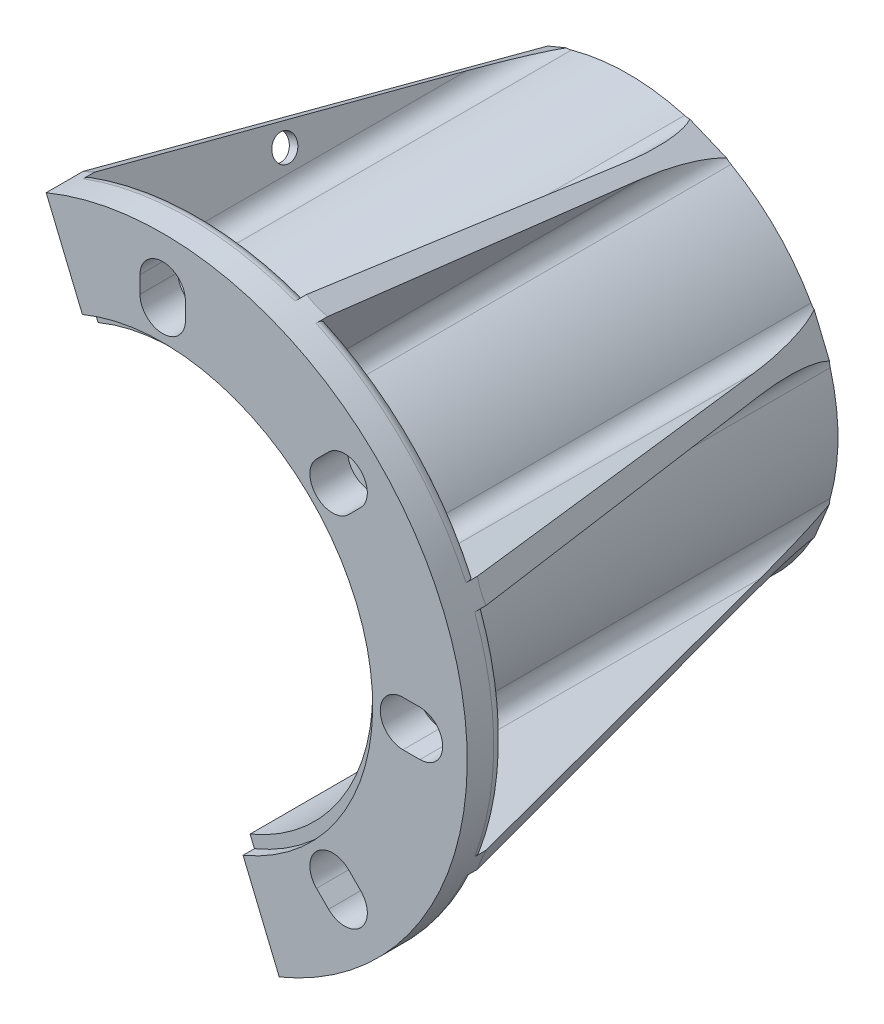
SolidWorks part; units mm, degrees
ref_plane "Front Plane" through (0, 0, 0) normal (0, 0, 1) x (1, 0, 0)
ref_plane "Top Plane" through (0, 0, 0) normal (0, 1, 0) x (1, 0, 0)
ref_plane "Right Plane" through (0, 0, 0) normal (1, 0, 0) x (0, 0, -1)
sketch "Sketch1" plane through (0, 0, 0) normal (0, 0, 1) x (1, 0, 0)
  line L0 (0, 0) -> (0, 80.5) construction
  line L1 (-6, 68) -> (-6, 63.5)
  line L2 (6, 68) -> (6, 63.5)
  line L3 (43.8406, 52.3259) -> (40.6586, 49.1439)
  line L4 (52.3259, 43.8406) -> (49.1439, 40.6586)
  line L5 (68, 6) -> (63.5, 6)
  line L6 (68, -6) -> (63.5, -6)
  line L7 (52.3259, -43.8406) -> (49.1439, -40.6586)
  line L8 (43.8406, -52.3259) -> (40.6586, -49.1439)
  line L9 (6, -68) -> (6, -63.5)
  line L10 (-6, -68) -> (-6, -63.5)
  line L11 (-43.8406, -52.3259) -> (-40.6586, -49.1439)
  line L12 (-52.3259, -43.8406) -> (-49.1439, -40.6586)
  line L13 (-68, -6) -> (-63.5, -6)
  line L14 (-68, 6) -> (-63.5, 6)
  line L15 (-52.3259, 43.8406) -> (-49.1439, 40.6586)
  line L16 (-43.8406, 52.3259) -> (-40.6586, 49.1439)
  circle A0 centre (0, 0) radius 55.5
  circle A1 centre (0, 0) radius 80.5
  circle A2 centre (0, 0) radius 68 construction
  circle A3 centre (0, 63.5) radius 6
  circle A4 centre (0, 68) radius 6
  circle A5 centre (0, 0) radius 63.5 construction
  circle A6 centre (48.0833, 48.0833) radius 6
  circle A7 centre (44.9013, 44.9013) radius 6
  circle A8 centre (68, 0) radius 6
  circle A9 centre (63.5, 0) radius 6
  circle A10 centre (48.0833, -48.0833) radius 6
  circle A11 centre (44.9013, -44.9013) radius 6
  circle A12 centre (0, -68) radius 6
  circle A13 centre (0, -63.5) radius 6
  circle A14 centre (-48.0833, -48.0833) radius 6
  circle A15 centre (-44.9013, -44.9013) radius 6
  circle A16 centre (-68, 0) radius 6
  circle A17 centre (-63.5, 0) radius 6
  circle A18 centre (-48.0833, 48.0833) radius 6
  circle A19 centre (-44.9013, 44.9013) radius 6
  point P73 (0, 0)
  dimension "D1" = 111
  dimension "D2" = 25
  dimension "D3" = 12.5
  dimension "D4" = 12
  dimension "D5" = 12
  dimension "D6" = 8
  dimension "D7" = 8
extrude "Boss-Extrude1" add sketch "Sketch1" along normal blind 10 contours A1 A19 L15 A18 L16 A17 L13 A16 L14 A15 L11 A14 L12 A13 L9 A12 L10 A11 L7 A10 L8 A9 L5 A8 L6 A7 L3 A6 L4 A4 L2 A3 L1 A0 region at (-78.2231, 0, 0)
ref_plane "Plane1" through (0, 0, 7) normal (0, 0, 1) x (1, 0, 0)
sketch "Sketch2" plane through (0, 0, 7) normal (0, 0, 1) x (1, 0, 0)
  circle A0 centre (0, 0) radius 55.5
  circle A1 centre (0, 0) radius 52.5
  circle A2 centre (0, 0) radius 55.5 construction
  dimension "D1" = 3
extrude "Boss-Extrude2" add sketch "Sketch2" against normal blind 120
sketch "Sketch6" plane through (0, 0, 0) normal (0, 0, -1) x (-1, 0, 0)
  line L0 (0, 0) -> (0, 80.5) construction
  line L1 (0, 0) -> (52.3259, 52.3259) construction
  line L2 (0, 0) -> (56.9221, 56.9221) construction
  line L3 (0, 80.5) -> (56.9221, 56.9221) construction
  line L4 (28.461, 68.711) -> (0, 0) construction
  line L5 (28.013, 75.4687) -> (19.3133, 52.0312)
  line L6 (33.5563, 73.1726) -> (23.1351, 50.4482)
  circle A0 centre (0, 0) radius 80.5 construction
  arc A1 (52.3259, 43.8406) -> (43.8406, 52.3259) centre (48.0833, 48.0833) ccw construction
  circle A2 centre (0, 0) radius 55.5 construction
  arc A3 (0, 80.5) -> (56.9221, 56.9221) centre (0, 0) ccw
  arc A4 (23.1351, 50.4482) -> (19.3133, 52.0312) centre (0, 0) ccw
  arc A5 (33.5563, 73.1726) -> (28.013, 75.4687) centre (0, 0) ccw
  arc A6 (0, 55.5) -> (39.2444, 39.2444) centre (0, 0) ccw
  circle M35 centre (0, 0) radius 55.5
  circle M36 centre (0, 0) radius 80.5
  dimension "D1" = 6
extrude "Boss-Extrude3" add sketch "Sketch6" along normal up to surface (113 mm away) contours L6 L5 M36 M35 region at (-26.3095, 63.5167, 0) up to face at (52.5, 0, -113)
ref_plane "Plane2" through (-29.35, 70.8572, -16.9562) normal (0.3737, -0.9021, 0.2159) x (-0.9276, -0.3634, 0.087)
sketch "Sketch7" plane through (-29.35, 70.8572, -16.9562) normal (0.3737, -0.9021, 0.2159) x (-0.9276, -0.3634, 0.087)
  circle A0 centre (-10.8246, 97.7875) radius 250
  dimension "D1" = 500
extrude "Cut-Extrude1" cut sketch "Sketch7" against normal through all
pattern_circular "CirPattern1" count 8 over 360 about axis through (0, 0, -113) along (0, 0, 1) of "Boss-Extrude3", "Cut-Extrude1"
fillet "Fillet1" radius 5 2 edges at (-19.3133, -52.0312, -56.5) (19.3133, -52.0312, -56.5)
fillet "Fillet2" radius 5 2 edges at (50.4482, -23.1351, -56.5) (23.1351, -50.4482, -56.5)
fillet "Fillet3" radius 5 2 edges at (52.0312, -19.3133, -56.5) (52.0312, 19.3133, -56.5)
fillet "Fillet4" radius 5 2 edges at (50.4482, 23.1351, -56.5) (23.1351, 50.4482, -56.5)
fillet "Fillet5" radius 5 2 edges at (19.3133, 52.0312, -56.5) (-19.3133, 52.0312, -56.5)
fillet "Fillet6" radius 5 2 edges at (-23.1351, 50.4482, -56.5) (-50.4482, 23.1351, -56.5)
fillet "Fillet7" radius 5 2 edges at (-52.0312, 19.3133, -56.5) (-52.0312, -19.3133, -56.5)
fillet "Fillet8" radius 5 2 edges at (-50.4482, -23.1351, -56.5) (-23.1351, -50.4482, -56.5)
ref_plane "Plane3" through (-2.7715, -1.148, -0.0247) normal (-0.9238, -0.3827, -0.0082) x (-0.0076, -0.0032, 1)
ref_plane "Plane4" through (2.7715, 1.148, -0.0247) normal (0.9238, 0.3827, -0.0082) x (-0.0076, -0.0032, -1)
ref_plane "Plane5" through (0, 0, 0) normal (0.9239, 0.3827, 0) x (0, 0, -1)
sketch "Sketch10" plane through (0, 0, 0) normal (0.9375, 0.348, 0) x (0, 0, -1)
  line L0 (0, 60.293) -> (91.3355, 60.293) construction
  line L1 (0, 80.5) -> (0, 60.293) construction
  circle A0 centre (45, 65.293) radius 3.25
  dimension "D1" = 6.5
  dimension "D2" = 5
  dimension "D3" = 45
extrude "Cut-Extrude2" cut sketch "Sketch10" against normal through all
ref_axis "Axis1" through (0, 0, -113) along (0, 0, 1)
ref_plane "Plane6" through (0, 0, 0) normal (-0.3827, 0.9239, 0) x (0, 0, 1)
mirror "Mirror1" about plane through (0, 0, 0) normal (-0.3827, 0.9239, 0) of "Cut-Extrude2"
fillet "Fillet10" radius 3 8 edges at (0, 80.5, 0) (0, -80.5, 0) (56.9221, -56.9221, 0) (56.9221, 56.9221, 0) (80.5, 0, 0) (-56.9221, 56.9221, 0) (-80.5, 0, 0) (-56.9221, -56.9221, 0)
sketch "Sketch11" plane through (0, 0, 0) normal (0, 0, -1) x (-1, 0, 0)
  line L0 (0, 0) -> (45.922, 110.8655) construction
  line L1 (0, 0) -> (45.922, 110.8655)
  line L2 (45.922, 110.8655) -> (156.7876, 64.9435)
  line L3 (156.7876, 64.9435) -> (64.9435, -156.7876)
  line L4 (64.9435, -156.7876) -> (-45.922, -110.8655)
  line L5 (21.0476, 50.8134) -> (-21.0476, -50.8134) construction
  line L6 (-45.922, -110.8655) -> (0, 0)
  dimension "D1" = 120
  dimension "D2" = 120
  dimension "D3" = 120
extrude "Cut-Extrude3" cut sketch "Sketch11" against normal through all both and the other way through all
